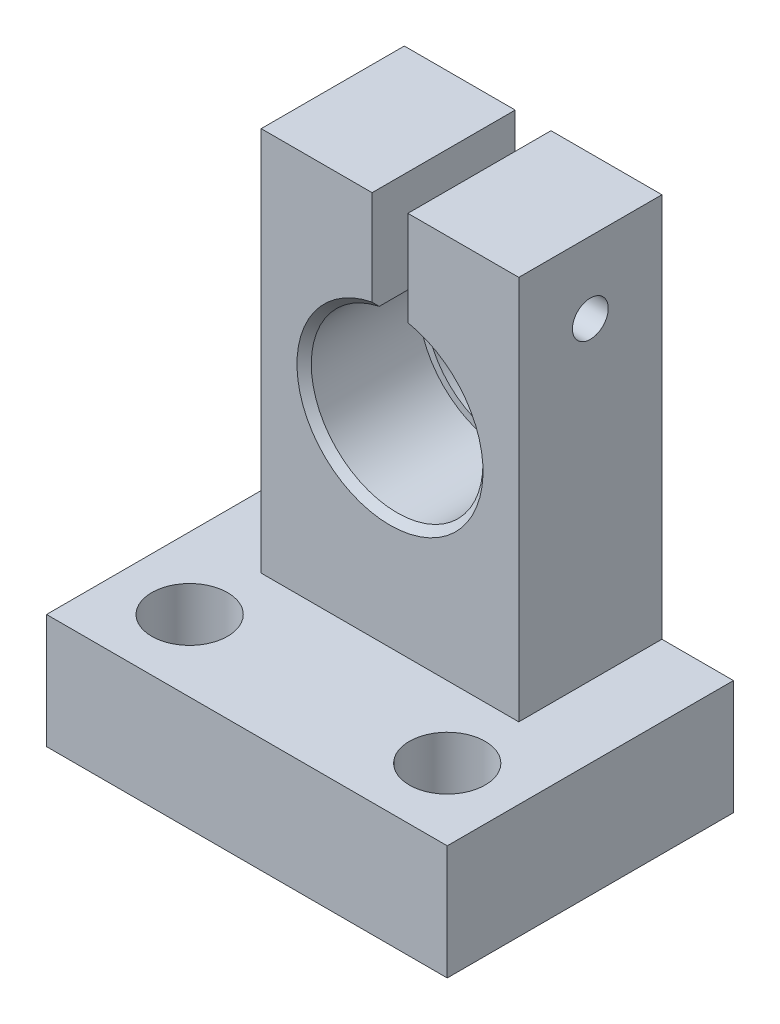
SolidWorks part; units mm, degrees
material "AISI 1045 Steel, cold drawn"
ref_plane "Front Plane" through (0, 0, 0) normal (0, 0, 1) x (1, 0, 0)
ref_plane "Top Plane" through (0, 0, 0) normal (0, 1, 0) x (1, 0, 0)
ref_plane "Right Plane" through (0, 0, 0) normal (1, 0, 0) x (0, 0, -1)
sketch "Sketch1" plane through (0, 0, 0) normal (0, 0, 1) x (1, 0, 0)
  line L1 (9, -21.9) -> (-9, -21.9)
  line L2 (9, -21.9) -> (9, 13)
  line L3 (9, 13) -> (-9, 13)
  line L4 (-9, -21.9) -> (-9, 13)
  line L5 (9, -21.9) -> (-9, 13) construction
  line L6 (9, 13) -> (-9, -21.9) construction
  circle A0 centre (0, 0) radius 6
  point P3 (0, -4.45)
  dimension "D1" = 12
  dimension "D2" = 13
  dimension "D3" = 21.9
  dimension "D4" = 18
extrude "Boss-Extrude1" add sketch "Sketch1" along normal blind 10
sketch "Sketch2" plane through (0, 0, 0) normal (0, 0, -1) x (-1, 0, 0)
  circle A0 centre (0, 0) radius 6 construction
  circle A1 centre (0, 0) radius 6
  circle A2 centre (0, 0) radius 5.5
  dimension "D1" = 0.5
extrude "Boss-Extrude2" add sketch "Sketch2" against normal blind 2
sketch "Sketch3" plane through (0, 0, 10) normal (0, 0, 1) x (1, 0, 0)
  line L0 (9, 13) -> (-9, 13) construction
  line L1 (1.25, 5.3561) -> (-1.25, 5.3561)
  line L2 (1.25, 5.3561) -> (1.25, 13)
  line L3 (1.25, 13) -> (-1.25, 13)
  line L4 (-1.25, 5.3561) -> (-1.25, 13)
  line L5 (1.25, 5.3561) -> (-1.25, 13) construction
  line L6 (1.25, 13) -> (-1.25, 5.3561) construction
  circle A0 centre (0, 0) radius 5.5 construction
  point P0 (0, 9.178)
  dimension "D1" = 2.5
extrude "Cut-Extrude1" cut sketch "Sketch3" against normal through all
hole_wizard "CBORE for M3 SHCS1" positions "Sketch4" profile "Sketch5" counterbore size "M3" standard "ANSI Metric" end condition up to next
sketch "Sketch4" plane through (9, 0, 0) normal (1, 0, 0) x (0, 0, -1)
  line L0 (0, -21.9) -> (0, 13) construction
  line L1 (-10, 13) -> (0, 13) construction
  point P0 (-5, 8)
  dimension "D1" = 5
  dimension "D2" = 5
sketch "Sketch5" plane through (9, 8, 5) normal (0, 1, 0) x (0, 0, -1)
  line L0 (0, 0) -> (0, 7.75)
  line L1 (0, 7.75) -> (1.6, 7.75)
  line L3 (1.6, 7.75) -> (1.6, 3)
  line L4 (1.6, 3) -> (3.25, 3)
  line L5 (3.25, 3) -> (3.25, 0)
  line L7 (3.25, 0) -> (0, 0)
  line L11 (0, -6.35) -> (0, 107.95) construction
  dimension "Thru Hole Dia." = 3.2
  dimension "Thru Hole Depth" = 7.75
  dimension "C'Bore Dia." = 6.5
  dimension "C'Bore Depth" = 3
chamfer "Chamfer1" distance 0.5 angle 45 1 edges at (0, -6, 10)
sketch "Sketch11" plane through (-9, 0, 0) normal (-1, 0, 0) x (0, 0, 1)
  line L0 (0, 13) -> (0, -21.9) construction
  line L1 (0, -21.9) -> (10, -21.9)
  line L2 (0, -21.9) -> (0, -13.9)
  line L3 (0, -13.9) -> (10, -13.9)
  line L4 (10, -21.9) -> (10, -13.9)
  line L5 (10, 13) -> (10, -21.9) construction
  dimension "D1" = 8
extrude "Boss-Extrude4" add sketch "Sketch11" along normal blind 5
mirror "Mirror1" about plane through (0, 0, 0) normal (1, 0, 0) of "Boss-Extrude4"
sketch "Sketch8" plane through (0, -21.9, 0) normal (0, -1, 0) x (1, 0, 0)
  line L0 (-14, 0) -> (-14, 10) construction
  line L1 (-14, 10) -> (14, 10)
  line L2 (-14, 10) -> (-14, 20)
  line L3 (-14, 20) -> (14, 20)
  line L4 (14, 10) -> (14, 20)
  dimension "D1" = 10
extrude "Boss-Extrude3" add sketch "Sketch8" against normal up to surface (8 mm away) up to face at (-11.5, -13.9, 5)
hole_wizard "M5 Clearance Hole1" positions "Sketch9" profile "Sketch10" hole size "M5" standard "ANSI Metric" end condition up to next
sketch "Sketch9" plane through (0, -13.9, 0) normal (0, 1, 0) x (1, 0, 0)
  line L0 (14, -20) -> (-14, -20) construction
  line L1 (-14, -20) -> (-14, 0) construction
  line L2 (0, -10) -> (0, -20) construction
  line L4 (-9, -10) -> (9, -10) construction
  point P0 (-9, -15)
  point P14 (9, -15)
  dimension "D1" = 5
  dimension "D2" = 5
sketch "Sketch10" plane through (-9, -13.9, 15) normal (1, 0, 0) x (0, 0, 1)
  line L0 (0, 0) -> (0, 8)
  line L1 (0, 8) -> (2.65, 8)
  line L2 (2.65, 8) -> (2.65, 0)
  line L5 (2.65, 0) -> (0, 0)
  line L11 (0, -6.35) -> (0, 107.95) construction
  dimension "Thru Hole Dia." = 5.3
  dimension "Thru Hole Depth" = 8
mirror "Mirror2" about plane through (14, 0, 0) normal (-1, 0, 0) of bodies 107
delete or keep bodies "Body-Delete/Keep 1" type delete bodies bodies 107
hole_wizard "M3x0.5 Tapped Hole1" positions "Sketch6" profile "Sketch7" tap size "M3x0.5" standard "ANSI Metric" end condition up to next
sketch "Sketch6" plane through (37, 0, 0) normal (-1, 0, 0) x (0, 0, 1)
  point P0 (5, 8)
  point P8 (5, 8)
cosmetic thread "Hole Thread6" parameters "D2"=3
sketch "Sketch7" plane through (37, 8, 5) normal (0, 1, 0) x (0, 0, -1)
  line L0 (0, 0) -> (0, 7.75)
  line L1 (0, 7.75) -> (1.25, 7.75)
  line L2 (1.25, 7.75) -> (1.25, 0)
  line L5 (1.25, 0) -> (0, 0)
  line L11 (0, -6.35) -> (0, 107.95) construction
  dimension "Thru Tap Drill Dia." = 2.5
  dimension "Thru Tap Drill Depth" = 7.75
